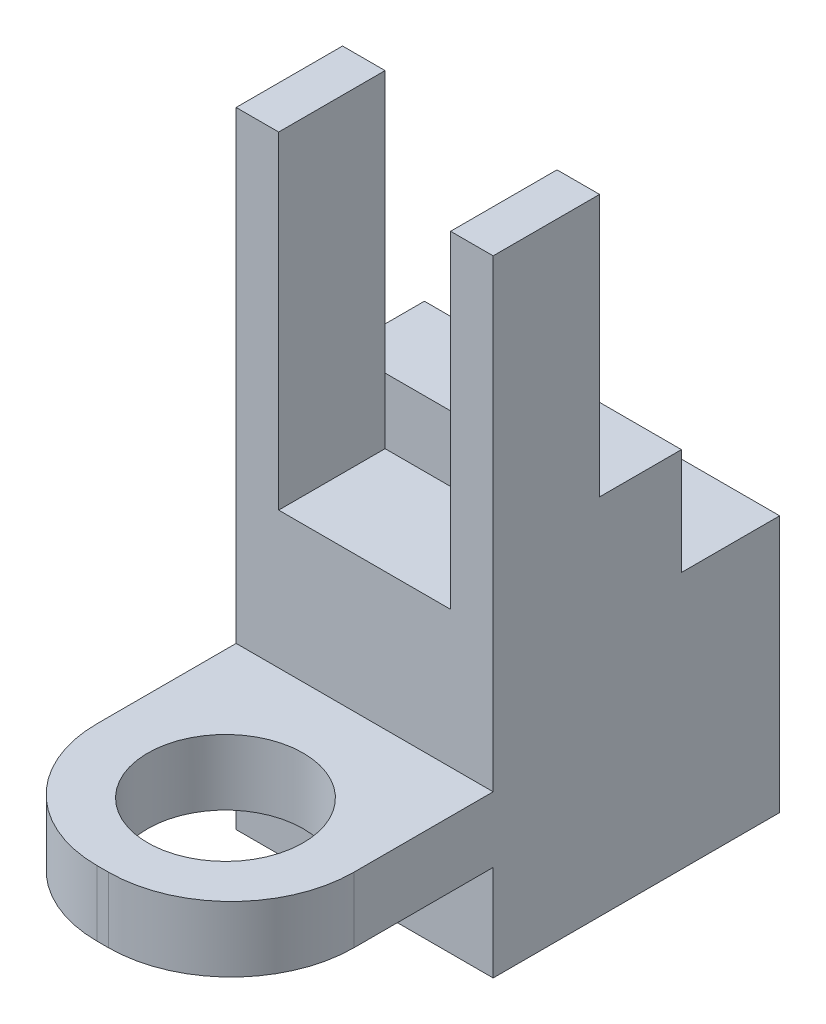
SolidWorks part; units mm, degrees
ref_plane "Front Plane" through (0, 0, 0) normal (0, 0, 1) x (1, 0, 0)
ref_plane "Top Plane" through (0, 0, 0) normal (0, 1, 0) x (1, 0, 0)
ref_plane "Right Plane" through (0, 0, 0) normal (1, 0, 0) x (0, 0, -1)
sketch "Sketch4" plane through (0, 0, 0) normal (0, 0, 1) x (1, 0, 0)
  line L0 (0, 82.063) -> (0, -112.4411) construction
  line L1 (-144.2959, 0) -> (145.5617, 0) construction
  line L2 (-12.7, 12.7) -> (-12.7, -12.7)
  line L3 (-15.7, 15.7) -> (15.7, 15.7)
  line L4 (-15.7, 15.7) -> (-15.7, -15.7)
  line L5 (-15.7, -15.7) -> (15.7, -15.7)
  line L6 (15.7, 15.7) -> (15.7, -15.7)
  line L7 (-12.7, -12.7) -> (12.7, -12.7)
  line L8 (12.7, 12.7) -> (12.7, -12.7)
  line L9 (-12.7, 12.7) -> (12.7, 12.7)
  dimension "D2" = 12.7
  dimension "D3" = 12.7
  dimension "D4" = 12.7
  dimension "D5" = 12.7
  dimension "D1" = 3
extrude "Boss-Extrude3" add sketch "Sketch4" along normal blind 30
sketch "Sketch5" plane through (0, 0, 30) normal (0, 0, 1) x (1, 0, 0)
  line L0 (-15.7, 15.7) -> (15.7, 15.7)
  line L1 (15.7, 15.7) -> (15.7, -15.7)
  line L2 (15.7, -15.7) -> (-15.7, -15.7)
  line L3 (-15.7, -15.7) -> (-15.7, 15.7)
extrude "Boss-Extrude4" add sketch "Sketch5" along normal blind 5
sketch "Sketch6" plane through (0, 0, 35) normal (0, 0, 1) x (1, 0, 0)
  line L0 (-14.6567, 0) -> (15.7, 0) construction
  line L1 (15.7, -15.7) -> (15.7, 15.7) construction
  line L2 (-15.7, 4) -> (15.7, 4)
  line L3 (-15.7, 15.7) -> (-15.7, -15.7) construction
  line L4 (15.7, 4) -> (15.7, -4)
  line L5 (15.7, -4) -> (-15.7, -4)
  line L6 (-15.7, -4) -> (-15.7, 4)
  dimension "D1" = 4
  dimension "D2" = 4
extrude "Boss-Extrude5" add sketch "Sketch6" along normal blind 5
sketch "Sketch7" plane through (0, -4, 0) normal (0, -1, 0) x (1, 0, 0)
  line L0 (-15.7, 40) -> (-15.7, 52)
  line L1 (-0.7, 67) -> (0.7, 67)
  line L2 (15.7, 52) -> (15.7, 40)
  line L3 (-15.7, 40) -> (15.7, 40) construction
  line L4 (15.7, 40) -> (-15.7, 40)
  line L5 (0, 0) -> (0, 92.3619) construction
  arc A0 (0.7, 67) -> (15.7, 52) centre (0.7, 52) cw
  arc A1 (-15.7, 52) -> (-0.7, 67) centre (-0.7, 52) cw
  point P9 (15.7, 67)
  point P12 (-15.7, 67)
  dimension "D3" = 15
  dimension "D1" = 27
  dimension "D2" = 31.4
extrude "Boss-Extrude6" add sketch "Sketch7" against normal blind 8
sketch "Sketch8" plane through (0, -4, 0) normal (0, -1, 0) x (1, 0, 0)
  line L0 (0, 67.4318) -> (0, -5.9603) construction
  line L1 (0.7, 67) -> (-0.7, 67) construction
  circle A0 centre (0, 52) radius 9.5
  dimension "D1" = 15
extrude "Boss-Extrude7" add sketch "Sketch8" along normal blind 8
mirror "Mirror1" about plane through (0, 0, 0) normal (0, 1, 0) of "Boss-Extrude7"
sketch "Sketch9" plane through (0, 15.7, 0) normal (0, 1, 0) x (1, 0, 0)
  line L1 (-15.7, -32) -> (15.7, -32)
  line L2 (-15.7, -35) -> (-15.7, 0) construction
  line L3 (15.7, -35) -> (15.7, 0) construction
  line L4 (0, 15.8647) -> (0, -78.6922) construction
  line L5 (0, -52) -> (31.7707, -52) construction
  line L6 (31.7707, -52) -> (-30.9902, -52) construction
  line L7 (-15.7, -32) -> (-15.7, -22)
  line L8 (-15.7, -22) -> (15.7, -22)
  line L9 (15.7, -22) -> (15.7, -32)
  dimension "D1" = 20
  dimension "D2" = 10
extrude "Boss-Extrude8" add sketch "Sketch9" along normal blind 5
sketch "Sketch10" plane through (0, 15.7, 0) normal (0, 1, 0) x (1, 0, 0)
  line L0 (-15.7, -22) -> (-15.7, -12)
  line L1 (-15.7, -22) -> (-15.7, 0) construction
  line L2 (-15.7, -12) -> (15.7, -12)
  line L3 (15.7, -22) -> (15.7, 0) construction
  line L4 (15.7, -12) -> (15.7, -22)
  line L5 (15.7, -22) -> (-15.7, -22)
  dimension "D1" = 10
extrude "Boss-Extrude9" add sketch "Sketch10" along normal blind 13
sketch "Sketch11" plane through (0, 20.7, 0) normal (0, 1, 0) x (1, 0, 0)
  line L0 (-15.7, -22) -> (-10.5, -22)
  line L1 (15.7, -22) -> (-15.7, -22) construction
  line L2 (-10.5, -22) -> (-10.5, -32)
  line L3 (-15.7, -32) -> (15.7, -32) construction
  line L4 (-10.5, -32) -> (-15.7, -32)
  line L5 (-15.7, -32) -> (-15.7, -22)
  line L6 (10.5, -22) -> (10.5, -32)
  line L7 (-15.7, -22) -> (15.7, -22) construction
  line L8 (-15.7, -32) -> (15.7, -32) construction
  line L9 (10.5, -32) -> (15.7, -32)
  line L10 (15.7, -32) -> (15.7, -22)
  line L11 (15.7, -32) -> (15.7, -22) construction
  line L12 (15.7, -22) -> (10.5, -22)
  dimension "D1" = 5.2
  dimension "D2" = 5.2
extrude "Boss-Extrude10" add sketch "Sketch11" along normal blind 40
sketch "Sketch12" plane through (0, 0, 32) normal (0, 0, 1) x (1, 0, 0)
  line L0 (-15.7, 60.7) -> (-10.5, 60.7)
  line L1 (-10.5, 60.7) -> (-10.5, 20.7)
  line L2 (-10.5, 20.7) -> (10.5, 20.7)
  line L3 (10.5, 20.7) -> (10.5, 60.7)
  line L4 (10.5, 60.7) -> (15.7, 60.7)
  line L5 (15.7, 60.7) -> (15.7, 15.7)
  line L6 (15.7, 15.7) -> (-15.7, 15.7)
  line L7 (-15.7, 15.7) -> (-15.7, 60.7)
extrude "Boss-Extrude11" add sketch "Sketch12" along normal blind 3
extrude "Cut-Extrude1" cut sketch "Sketch8<2>" against normal blind 24 from offset 8
sketch "Sketch8<2>" plane through (0, -4, 0) normal (0, -1, 0) x (1, 0, 0) same geometry as "Sketch8"
